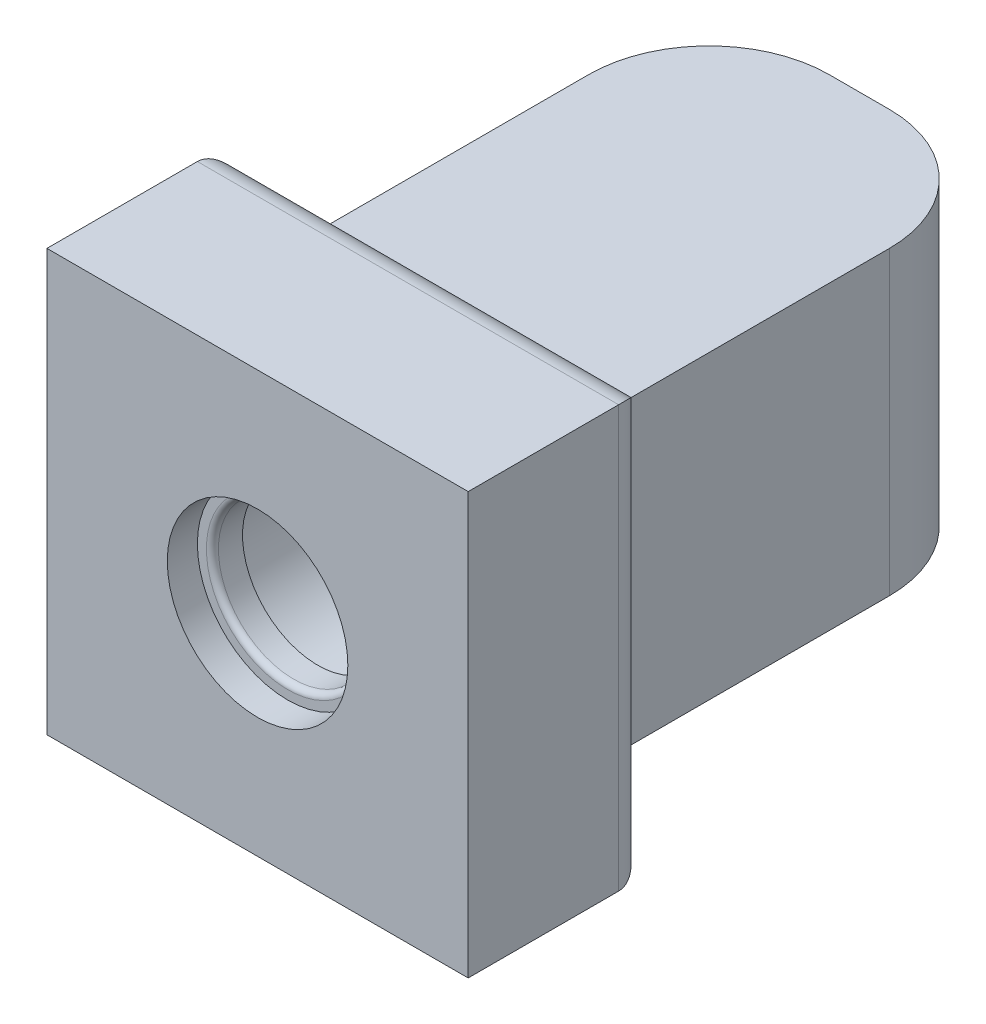
SolidWorks part; units mm, degrees
ref_plane "Plan de face" through (0, 0, 0) normal (0, 0, 1) x (1, 0, 0)
ref_plane "Plan de dessus" through (0, 0, 0) normal (0, 1, 0) x (1, 0, 0)
ref_plane "Plan de droite" through (0, 0, 0) normal (1, 0, 0) x (0, 0, -1)
sketch "Esquisse4" plane through (0, 0, 0) normal (0, 1, 0) x (1, 0, 0)
  line L1 (-0.5, 3.5) -> (0.5, 3.5)
  line L2 (-2.5, 1.5) -> (-2.5, -3.5)
  line L3 (-2.5, -3.5) -> (2.5, -3.5)
  line L4 (2.5, 1.5) -> (2.5, -3.5)
  line L5 (-2.5, 3.5) -> (2.5, -3.5) construction
  line L6 (-2.5, -3.5) -> (2.5, 3.5) construction
  arc A0 (0.5, 3.5) -> (2.5, 1.5) centre (0.5, 1.5) cw
  arc A1 (-0.5, 3.5) -> (-2.5, 1.5) centre (-0.5, 1.5) ccw
  circle A2 centre (0, 0.05) radius 1.5
  point P0 (0, 0)
  dimension "D3" = 2
  dimension "D5" = 3
  dimension "D1" = 7
  dimension "D2" = 5
  dimension "D4" = 3.55
extrude "Boss.-Extru.2" add sketch "Esquisse4" along normal blind 5
sketch "Esquisse5" plane through (0, 5, 0) normal (0, 1, 0) x (1, 0, 0)
  circle A0 centre (0, 0.05) radius 1.5 construction
  circle A1 centre (0, 0.05) radius 1.5
extrude "Boss.-Extru.3" add sketch "Esquisse5" against normal blind 2
sketch "Esquisse6" plane through (0, 0, 3.5) normal (0, 0, 1) x (1, 0, 0)
  line L0 (-3.5, -1) -> (3.5, -1)
  line L1 (3.5, -1) -> (3.5, 6)
  line L2 (3.5, 6) -> (-3.5, 6)
  line L3 (-3.5, 6) -> (-3.5, -1)
extrude "Boss.-Extru.4" add sketch "Esquisse6" along normal blind 3
fillet "Congé1" radius 0.5 8 edges at (0, 5, 3.5) (2.5, 2.5, 3.5) (0, 0, 3.5) (-2.5, 2.5, 3.5) (0, -1, 3.5) (3.5, 2.5, 3.5) (0, 6, 3.5) (-3.5, 2.5, 3.5)
sketch "Esquisse7" plane through (0, 0, 6.5) normal (0, 0, 1) x (1, 0, 0)
  line L0 (-3.5, 6) -> (3.5, -1) construction
  line L1 (-3.5, -1) -> (3.5, 6) construction
  circle A0 centre (0, 2.5) radius 1.5
  dimension "D1" = 3
extrude "Enlèv. mat.-Extru.1" cut sketch "Esquisse7" against normal blind 3
sketch "Esquisse8" plane through (0, 0, 6.5) normal (0, 0, 1) x (1, 0, 0)
  circle A0 centre (0, 2.5) radius 1.5 construction
  circle A1 centre (0, 2.5) radius 1.5
  circle A2 centre (0, 2.5) radius 1.25
  dimension "D1" = 0.25
extrude "Boss.-Extru.5" add sketch "Esquisse8" against normal blind 0.5 from offset 0.5 offset against normal yes
fillet "Congé2" radius 0.1 1 edges at (1.25, 2.5, 6)
